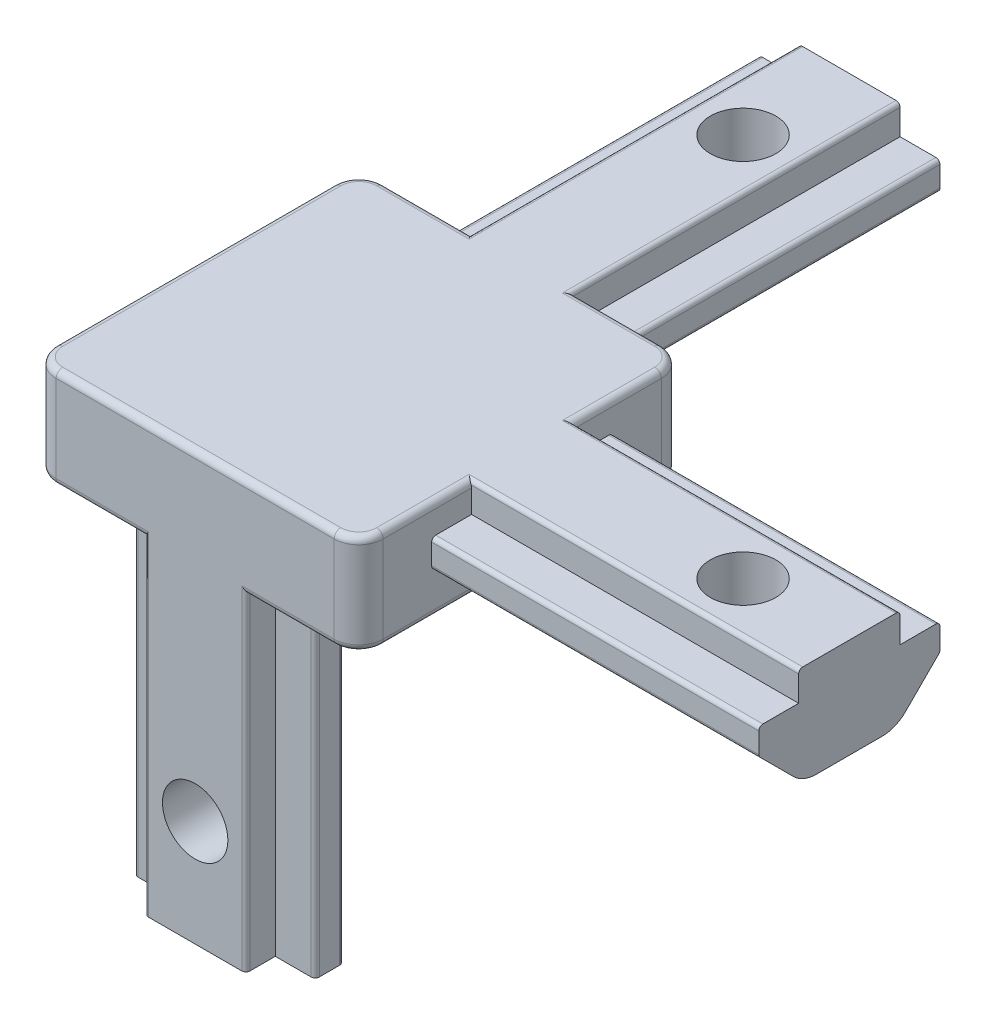
SolidWorks part; units mm, degrees
material "Stopy cynku 7; AG40B; Zn-4Al-0.015Mg"
ref_plane "Płaszczyzna przednia" through (0, 0, 0) normal (0, 0, 1) x (1, 0, 0)
ref_plane "Płaszczyzna górna" through (0, 0, 0) normal (0, 1, 0) x (1, 0, 0)
ref_plane "Płaszczyzna prawa" through (0, 0, 0) normal (1, 0, 0) x (0, 0, -1)
sketch "Szkic1" plane through (0, 0, 0) normal (0, 1, 0) x (1, 0, 0)
  line L0 (-33.7529, 22.2434) -> (-37.7747, 22.2434)
  line L1 (-39.189, 22.8292) -> (-41.3032, 24.9434)
  line L2 (-41.3032, 24.9434) -> (-41.3032, 26.5434)
  line L3 (-41.3032, 26.5434) -> (-38.8638, 26.5434)
  line L4 (-38.8638, 26.5434) -> (-38.8638, 27.8434)
  line L5 (-38.8638, 27.8434) -> (-39.1638, 27.8434)
  line L6 (-39.3638, 28.0434) -> (-39.3638, 28.3434)
  line L7 (-39.3638, 28.3434) -> (-44.2638, 28.3434)
  line L8 (-45.7638, 26.8434) -> (-45.7638, 21.9434)
  line L9 (-45.7638, 21.9434) -> (-45.4638, 21.9434)
  line L10 (-45.2638, 21.7434) -> (-45.2638, 21.4434)
  line L11 (-45.2638, 21.4434) -> (-43.9638, 21.4434)
  line L12 (-43.9638, 21.4434) -> (-43.9638, 23.8827)
  line L13 (-43.9638, 23.8827) -> (-42.3638, 23.8827)
  line L14 (-42.3638, 23.8827) -> (-40.2496, 21.7685)
  line L15 (-39.6638, 20.3543) -> (-39.6638, 16.3325)
  line L16 (-40.2496, 14.9183) -> (-42.3638, 12.804)
  line L17 (-42.3638, 12.804) -> (-43.9638, 12.804)
  line L18 (-43.9638, 12.804) -> (-43.9638, 15.2434)
  line L19 (-43.9638, 15.2434) -> (-45.2638, 15.2434)
  line L20 (-45.2638, 15.2434) -> (-45.2638, 14.9434)
  line L21 (-45.4638, 14.7434) -> (-45.7638, 14.7434)
  line L22 (-45.7638, 14.7434) -> (-45.7638, 9.8434)
  line L23 (-44.2638, 8.3434) -> (-39.3638, 8.3434)
  line L24 (-39.3638, 8.3434) -> (-39.3638, 8.6434)
  line L25 (-39.1638, 8.8434) -> (-38.8638, 8.8434)
  line L26 (-38.8638, 8.8434) -> (-38.8638, 10.1434)
  line L27 (-38.8638, 10.1434) -> (-41.3032, 10.1434)
  line L28 (-41.3032, 10.1434) -> (-41.3032, 11.7434)
  line L29 (-41.3032, 11.7434) -> (-39.189, 13.8576)
  line L30 (-37.7747, 14.4434) -> (-33.7529, 14.4434)
  line L31 (-32.3387, 13.8576) -> (-30.2245, 11.7434)
  line L32 (-30.2245, 11.7434) -> (-30.2245, 10.1434)
  line L33 (-30.2245, 10.1434) -> (-32.6638, 10.1434)
  line L34 (-32.6638, 10.1434) -> (-32.6638, 8.8434)
  line L35 (-32.6638, 8.8434) -> (-32.3638, 8.8434)
  line L36 (-32.1638, 8.6434) -> (-32.1638, 8.3434)
  line L37 (-32.1638, 8.3434) -> (-27.2638, 8.3434)
  line L38 (-25.7638, 9.8434) -> (-25.7638, 14.7434)
  line L39 (-25.7638, 14.7434) -> (-26.0638, 14.7434)
  line L40 (-26.2638, 14.9434) -> (-26.2638, 15.2434)
  line L41 (-26.2638, 15.2434) -> (-27.5638, 15.2434)
  line L42 (-27.5638, 15.2434) -> (-27.5638, 12.804)
  line L43 (-27.5638, 12.804) -> (-29.1638, 12.804)
  line L44 (-29.1638, 12.804) -> (-31.278, 14.9183)
  line L45 (-31.8638, 16.3325) -> (-31.8638, 20.3543)
  line L46 (-31.278, 21.7685) -> (-29.1638, 23.8827)
  line L47 (-29.1638, 23.8827) -> (-27.5638, 23.8827)
  line L48 (-27.5638, 23.8827) -> (-27.5638, 21.4434)
  line L49 (-27.5638, 21.4434) -> (-26.2638, 21.4434)
  line L50 (-26.2638, 21.4434) -> (-26.2638, 21.7434)
  line L51 (-26.0638, 21.9434) -> (-25.7638, 21.9434)
  line L52 (-25.7638, 21.9434) -> (-25.7638, 26.8434)
  line L53 (-27.2638, 28.3434) -> (-32.1638, 28.3434)
  line L54 (-32.1638, 28.3434) -> (-32.1638, 28.0434)
  line L55 (-32.3638, 27.8434) -> (-32.6638, 27.8434)
  line L56 (-32.6638, 27.8434) -> (-32.6638, 26.5434)
  line L57 (-32.6638, 26.5434) -> (-30.2245, 26.5434)
  line L58 (-30.2245, 26.5434) -> (-30.2245, 24.9434)
  line L59 (-30.2245, 24.9434) -> (-32.3387, 22.8292)
  line L60 (-45.2638, 21.4434) -> (-45.7638, 21.4434)
  line L61 (-45.7638, 21.4434) -> (-45.7638, 15.2434)
  line L62 (-45.7638, 15.2434) -> (-45.2638, 15.2434)
  line L63 (-38.8638, 8.8434) -> (-38.8638, 8.3434)
  line L64 (-38.8638, 8.3434) -> (-32.6638, 8.3434)
  line L65 (-32.6638, 8.3434) -> (-32.6638, 8.8434)
  line L66 (-39.3638, 28.3434) -> (-32.1638, 28.3434)
  line L67 (-25.7638, 21.9434) -> (-25.7638, 14.7434)
  line L68 (-32.1638, 8.3434) -> (-39.3638, 8.3434)
  line L69 (-45.7638, 14.7434) -> (-45.7638, 21.9434)
  line L70 (-38.8638, 27.8434) -> (-38.8638, 28.3434)
  line L71 (-38.8638, 28.3434) -> (-32.6638, 28.3434)
  line L72 (-32.6638, 28.3434) -> (-32.6638, 27.8434)
  line L73 (-26.2638, 21.4434) -> (-25.7638, 21.4434)
  line L74 (-25.7638, 21.4434) -> (-25.7638, 15.2434)
  line L75 (-25.7638, 15.2434) -> (-26.2638, 15.2434)
  arc A0 (-39.189, 22.8292) -> (-37.7747, 22.2434) centre (-37.7747, 24.2434) ccw
  arc A1 (-39.3638, 28.0434) -> (-39.1638, 27.8434) centre (-39.1638, 28.0434) ccw
  arc A2 (-44.2638, 28.3434) -> (-45.7638, 26.8434) centre (-44.2638, 26.8434) ccw
  arc A3 (-45.2638, 21.7434) -> (-45.4638, 21.9434) centre (-45.4638, 21.7434) ccw
  arc A4 (-39.6638, 20.3543) -> (-40.2496, 21.7685) centre (-41.6638, 20.3543) ccw
  arc A5 (-40.2496, 14.9183) -> (-39.6638, 16.3325) centre (-41.6638, 16.3325) ccw
  arc A6 (-45.4638, 14.7434) -> (-45.2638, 14.9434) centre (-45.4638, 14.9434) ccw
  arc A7 (-45.7638, 9.8434) -> (-44.2638, 8.3434) centre (-44.2638, 9.8434) ccw
  arc A8 (-39.1638, 8.8434) -> (-39.3638, 8.6434) centre (-39.1638, 8.6434) ccw
  arc A9 (-37.7747, 14.4434) -> (-39.189, 13.8576) centre (-37.7747, 12.4434) ccw
  arc A10 (-32.3387, 13.8576) -> (-33.7529, 14.4434) centre (-33.7529, 12.4434) ccw
  arc A11 (-32.1638, 8.6434) -> (-32.3638, 8.8434) centre (-32.3638, 8.6434) ccw
  arc A12 (-27.2638, 8.3434) -> (-25.7638, 9.8434) centre (-27.2638, 9.8434) ccw
  arc A13 (-26.2638, 14.9434) -> (-26.0638, 14.7434) centre (-26.0638, 14.9434) ccw
  arc A14 (-31.8638, 16.3325) -> (-31.278, 14.9183) centre (-29.8638, 16.3325) ccw
  arc A15 (-31.278, 21.7685) -> (-31.8638, 20.3543) centre (-29.8638, 20.3543) ccw
  arc A16 (-26.0638, 21.9434) -> (-26.2638, 21.7434) centre (-26.0638, 21.7434) ccw
  arc A17 (-25.7638, 26.8434) -> (-27.2638, 28.3434) centre (-27.2638, 26.8434) ccw
  arc A18 (-32.3638, 27.8434) -> (-32.1638, 28.0434) centre (-32.3638, 28.0434) ccw
  arc A19 (-33.7529, 22.2434) -> (-32.3387, 22.8292) centre (-33.7529, 24.2434) ccw
extrude "Dodanie-wyciągnięcie1" add sketch "Szkic1" along normal blind 6.1 contours A19 L0 A0 L1 L2 L3 L4 L5 A1 L6 L7 A2 L8 L9 A3 L10 L11 L12 L13 L14 A4 L15 A5 L16 L17 L18 L19 L20 A6 L21 L22 A7 L23 L24 A8 L25 L26 L27 L28 L29 A9 L30 A10 L31 L32 L33 L34 L35 A11 L36 L37 | L0 A19 L59 L58 L57 L56 L55 A18 L54 L66 L6 A1 L5 L4 L3 L2 L1 A0 | L31 A10 L30 A9 L29 L28 L27 L26 L63 L64 L65 L34 L33 L32 | L25 A8 L24 L68 L63 | L36 A11 L35 L65 L68 | L16 A5 L15 A4 L14 L13 L12 L11 L60 L61 L62 L19 L18 L17 | L51 A16 L50 L49 L48 L47 L46 A15 L45 A14 L44 L43 L42 L41 L40 A13 L39 L67 | L10 A3 L9 L69 L60 | L21 A6 L20 L62 L69 | L40 A13 L39 L67 L75 | L51 A16 L50 L73 L67 | L55 A18 L54 L66 L72 | L6 A1 L5 L70 L66 region at (-35.7638, 0, -18.3434) region at (-35.7638, 0, -25.2407) region at (-32.4211, 0, -28.1007) region at (-39.1065, 0, -28.1007) region at (-26.0065, 0, -21.6861) region at (-45.5211, 0, -21.6861) region at (-28.8665, 0, -18.3434) region at (-42.6612, 0, -18.3434) region at (-26.0065, 0, -15.0007) region at (-45.5211, 0, -15.0007) region at (-32.4211, 0, -8.5861) region at (-39.1065, 0, -8.5861) region at (-35.7638, 0, -11.446)
extrude "Dodanie-wyciągnięcie2" add sketch "Szkic1<4>" against normal blind 20 contours L16 A5 L15 A4 L14 L13 L12 L11 L60 L61 L62 L19 L18 L17 | L31 A10 L30 A9 L29 L28 L27 L26 L63 L64 L65 L34 L33 L32 region at (-42.6612, 0, -18.3434) region at (-35.7638, 0, -11.446)
sketch "Szkic1<4>" plane through (0, 0, 0) normal (0, 1, 0) x (1, 0, 0) same geometry as "Szkic1"
sketch "Szkic2" plane through (-25.7638, 0, 0) normal (1, 0, 0) x (0, 0, -1)
  line L0 (21.4434, 5.6) -> (21.4434, 4.3)
  line L1 (21.4434, 4.3) -> (23.8827, 4.3)
  line L2 (23.8827, 4.3) -> (23.8827, 2.7)
  line L3 (23.8827, 2.7) -> (21.7685, 0.5858)
  line L4 (20.3543, 0) -> (16.3325, 0)
  line L5 (14.9183, 0.5858) -> (12.804, 2.7)
  line L6 (12.804, 2.7) -> (12.804, 4.3)
  line L7 (12.804, 4.3) -> (15.2434, 4.3)
  line L8 (15.2434, 4.3) -> (15.2434, 5.6)
  line L9 (15.2434, 5.6) -> (15.2434, 6.1)
  line L10 (21.4434, 6.1) -> (21.4434, 5.6)
  line L11 (15.2434, 6.1) -> (21.4434, 6.1)
  line L12 (21.4434, 0) -> (21.4434, 6.1) construction
  line L13 (9.8434, 6.1) -> (26.8434, 6.1) construction
  line L14 (15.2434, 0) -> (15.2434, 6.1) construction
  line L15 (15.2434, 6.1) -> (21.4434, 6.1) construction
  arc A0 (20.3543, 0) -> (21.7685, 0.5858) centre (20.3543, 2) ccw
  arc A1 (14.9183, 0.5858) -> (16.3325, 0) centre (16.3325, 2) ccw
  point P24 (0, 0)
  point P25 (0, 0)
sketch "Szkic3" plane through (0, 0, -28.3434) normal (0, 0, -1) x (-1, 0, 0)
  line L0 (38.8638, 5.6) -> (38.8638, 4.3)
  line L1 (38.8638, 4.3) -> (41.3032, 4.3)
  line L2 (41.3032, 4.3) -> (41.3032, 2.7)
  line L3 (41.3032, 2.7) -> (39.189, 0.5858)
  line L4 (37.7747, 0) -> (33.7529, 0)
  line L5 (32.3387, 0.5858) -> (30.2245, 2.7)
  line L6 (30.2245, 2.7) -> (30.2245, 4.3)
  line L7 (30.2245, 4.3) -> (32.6638, 4.3)
  line L8 (32.6638, 4.3) -> (32.6638, 5.6)
  line L9 (32.6638, 5.6) -> (32.6638, 6.1)
  line L10 (38.8638, 6.1) -> (38.8638, 5.6)
  line L11 (32.6638, 6.1) -> (38.8638, 6.1)
  line L12 (38.8638, 0) -> (38.8638, 6.1) construction
  line L13 (32.6638, 0) -> (32.6638, 6.1) construction
  line L14 (32.6638, 6.1) -> (38.8638, 6.1) construction
  arc A0 (37.7747, 0) -> (39.189, 0.5858) centre (37.7747, 2) ccw
  arc A1 (32.3387, 0.5858) -> (33.7529, 0) centre (33.7529, 2) ccw
extrude "Dodanie-wyciągnięcie3" add sketch "Szkic2" along normal blind 20
extrude "Dodanie-wyciągnięcie4" add sketch "Szkic3" along normal blind 20
sketch "Szkic4" plane through (0, 6.1, 0) normal (0, 1, 0) x (1, 0, 0)
  line L0 (-5.7638, 18.3434) -> (-12.2638, 18.3434) construction
  line L1 (-5.7638, 21.4434) -> (-5.7638, 15.2434) construction
  line L2 (-35.7638, 48.3434) -> (-35.7638, 41.8434) construction
  line L3 (-38.8638, 48.3434) -> (-32.6638, 48.3434) construction
  circle A0 centre (-12.2638, 18.3434) radius 2
  circle A1 centre (-35.7638, 41.8434) radius 2
  dimension "D1" = 6.5
  dimension "D2" = 4
extrude "Wytnij-wyciągnięcie1" cut sketch "Szkic4" against normal up to next
sketch "Szkic5" plane through (0, 0, -8.3434) normal (0, 0, 1) x (1, 0, 0)
  line L0 (-35.7638, -20) -> (-35.7638, -13.5) construction
  line L1 (-38.8638, -20) -> (-32.6638, -20) construction
  circle A0 centre (-35.7638, -13.5) radius 2
extrude "Wytnij-wyciągnięcie2" cut sketch "Szkic5" against normal up to next
sketch "Szkic6" plane through (-45.7638, 0, 0) normal (-1, 0, 0) x (0, 0, 1)
  line L0 (-18.3434, -20) -> (-18.3434, -13.5) construction
  line L1 (-21.4434, -20) -> (-15.2434, -20) construction
  circle A0 centre (-18.3434, -13.5) radius 2
extrude "Wytnij-wyciągnięcie3" cut sketch "Szkic6" against normal up to next
fillet "Zaokrąglenie1" radius 0.4 22 edges at (-29.9638, 6.1, -28.3434) (-26.2032, 6.1, -27.904) (-41.5638, 6.1, -28.3434) (-45.3245, 6.1, -27.904) (-25.7638, 6.1, -12.5434) (-26.2032, 6.1, -8.7827) (-35.7638, 6.1, -8.3434) (-45.3245, 6.1, -8.7827) (-25.7638, 6.1, -24.1434) (-45.7638, 6.1, -18.3434) (-30.5084, 0, -28.3434) (-26.2032, 0, -27.904) (-25.7638, 0, -13.0879) (-26.2032, 0, -8.7827) (-41.5638, 0, -8.3434) (-45.3245, 0, -8.7827) (-41.0193, 0, -28.3434) (-45.3245, 0, -27.904) (-25.7638, 0, -23.5988) (-29.9638, 0, -8.3434) (-45.7638, 0, -12.5434) (-45.7638, 0, -24.1434)
fillet "Zaokrąglenie2" radius 0.25 24 edges at (-42.3638, -10, -12.804) (-42.3638, -10, -23.8827) (-43.9638, -10, -23.8827) (-45.7638, -9.8, -21.4434) (-45.7638, -9.8, -15.2434) (-43.9638, -10, -12.804) (-30.2245, -10, -11.7434) (-30.2245, -10, -10.1434) (-41.3032, -10, -11.7434) (-41.3032, -10, -10.1434) (-32.6638, -9.8, -8.3434) (-38.8638, -9.8, -8.3434) (-15.7638, 2.7, -12.804) (-15.7638, 2.7, -23.8827) (-15.7638, 4.3, -12.804) (-15.7638, 4.3, -23.8827) (-15.9638, 6.1, -21.4434) (-15.9638, 6.1, -15.2434) (-41.3032, 2.7, -38.3434) (-30.2245, 2.7, -38.3434) (-41.3032, 4.3, -38.3434) (-30.2245, 4.3, -38.3434) (-38.8638, 6.1, -38.1434) (-32.6638, 6.1, -38.1434)
